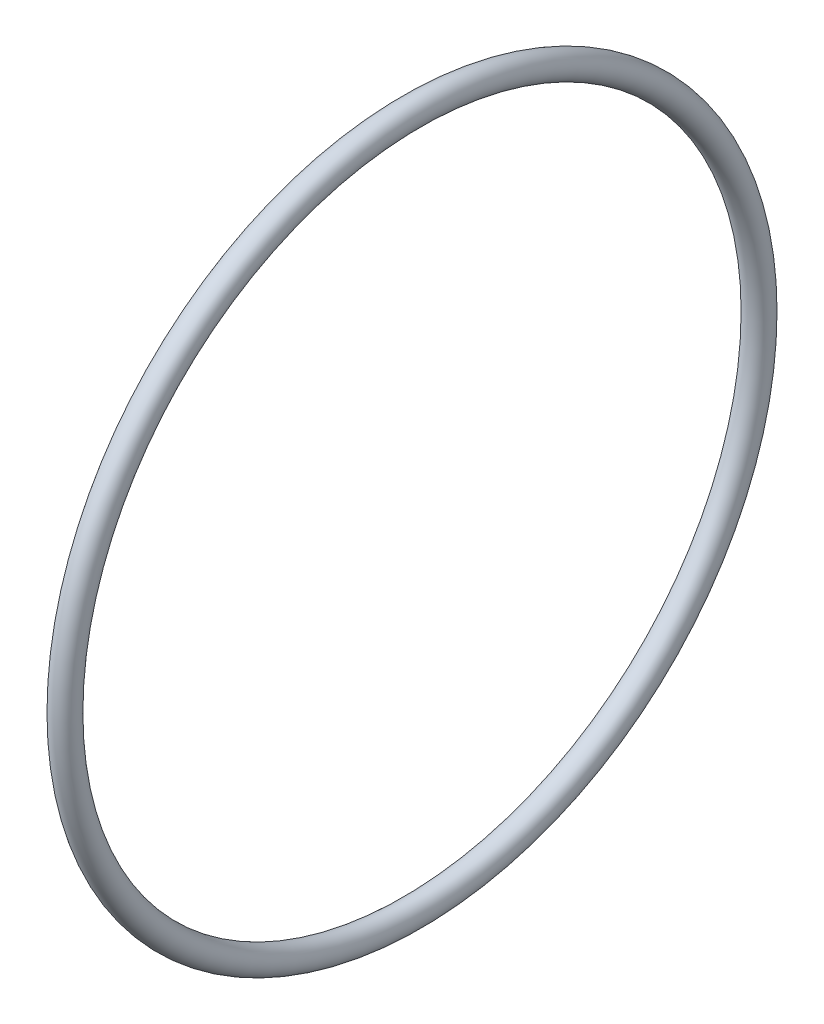
SolidWorks part; units mm, degrees
ref_plane "Front Plane" through (0, 0, 0) normal (0, 0, 1) x (1, 0, 0)
ref_plane "Top Plane" through (0, 0, 0) normal (0, 1, 0) x (1, 0, 0)
ref_plane "Right Plane" through (0, 0, 0) normal (1, 0, 0) x (0, 0, -1)
sketch "Sketch2" plane through (0, 0, 0) normal (0, 0, 1) x (1, 0, 0)
  line L0 (0, 0) -> (58.591, 0) construction
  line L2 (0, 0) -> (18.4, 0)
  line L3 (0, 0) -> (0, 2.5)
  line L4 (0, 2.5) -> (18.4, 2.5)
  line L5 (18.4, 0) -> (18.4, 2.5)
  line L6 (6, 2.5) -> (6, 6)
  line L11 (6, 6) -> (9.97, 6)
  line L16 (12.97, 6) -> (12.97, 3)
  line L17 (12.97, 3) -> (13.6304, 3)
  line L18 (13.6304, 3) -> (13.6304, 2.5)
  line L19 (13.6304, 2.5) -> (6, 2.5)
  line L22 (13.6304, 2.5) -> (16.1104, 2.5)
  line L23 (13.6304, 2.5) -> (13.6304, 4)
  line L24 (13.6304, 4) -> (16.1104, 4)
  line L25 (16.1104, 2.5) -> (16.1104, 4)
  line L27 (6, 6) -> (9.97, 6)
  line L28 (6, 6) -> (6, 9)
  line L29 (6, 9) -> (9.97, 9)
  line L30 (9.97, 6) -> (9.97, 9)
  line L31 (6, 9) -> (6, 8.25)
  line L32 (6, 8.25) -> (5, 8.25)
  line L33 (8.58, 22.001) -> (8.58, 12.476) construction
  line L34 (5, 12.476) -> (12.16, 12.476)
  line L35 (9.97, 9) -> (12.16, 9)
  line L36 (5, 7.5) -> (3, 7.5)
  line L37 (5, 8.25) -> (5, 12.476)
  line L38 (5, 7.5) -> (5, 14)
  line L39 (5, 14) -> (3, 14)
  line L40 (3, 7.5) -> (3, 14)
  line L41 (5, 22.001) -> (12.16, 22.001)
  line L42 (5, 22.001) -> (5, 30.1625)
  line L43 (5, 30.1625) -> (12.16, 30.1625)
  line L44 (12.16, 22.001) -> (12.16, 30.1625)
  line L49 (16.6304, 22.001) -> (16.6304, 7.5)
  line L51 (23.0104, 7.5) -> (23.0104, 6.5)
  line L54 (16.1104, 4) -> (13.6304, 4)
  line L56 (18.0304, 7.5) -> (23.0104, 7.5)
  line L57 (13.16, 22.001) -> (16.6304, 22.001)
  line L58 (16.1104, 3.5) -> (20.0104, 3.5)
  line L59 (29.9004, 14) -> (26.9004, 11)
  line L60 (4, 31.75) -> (18.0304, 31.75)
  line L61 (18.0304, 7.5) -> (23.0104, 7.5)
  line L62 (18.0304, 7.5) -> (18.0304, 12)
  line L63 (18.0304, 12) -> (23.0104, 12)
  line L64 (23.0104, 7.5) -> (23.0104, 12)
  line L65 (18.0304, 31.75) -> (18.0304, 12)
  line L66 (23.0104, 11) -> (26.9004, 11)
  line L67 (34.8004, 23) -> (31.3004, 19.5)
  line L68 (35.8004, 31) -> (38.7904, 33.99)
  line L69 (29.9004, 14) -> (29.9004, 15)
  line L70 (29.9004, 15) -> (22.9304, 15)
  line L71 (22.9304, 15) -> (21.0304, 15)
  line L72 (18.0304, 7.5) -> (16.6304, 7.5)
  line L73 (21.0304, 15) -> (21.0304, 43)
  line L74 (20.0304, 40) -> (10.0704, 40)
  line L75 (10.0704, 40) -> (4, 40)
  line L76 (21.0304, 43) -> (20.0304, 43)
  line L77 (22.9304, 15) -> (29.9004, 15)
  line L78 (22.9304, 15) -> (22.9304, 21)
  line L79 (22.9304, 21) -> (29.9004, 21)
  line L80 (29.9004, 15) -> (29.9004, 21)
  line L81 (10.0704, 40) -> (20.0304, 40)
  line L82 (10.0704, 40) -> (10.0704, 50)
  line L83 (10.0704, 50) -> (20.0304, 50)
  line L84 (20.0304, 40) -> (20.0304, 50)
  line L85 (4, 40) -> (4, 31.75)
  line L86 (12.97, 3) -> (12.97, 2.5)
  line L87 (31.3004, 19.5) -> (29.9004, 19.5)
  line L88 (21.51, 63.5) -> (21.51, 44)
  line L89 (21.51, 63.5) -> (25.9304, 63.5)
  line L90 (25.9304, 63.5) -> (25.9304, 25)
  line L91 (27.8304, 25) -> (25.9304, 25)
  line L92 (10.0704, 48) -> (9, 48)
  line L93 (9, 48) -> (9, 53.476)
  line L94 (9, 53.476) -> (20.0304, 53.476)
  line L95 (20.0304, 53.476) -> (20.0304, 50)
  line L96 (14.5152, 63.001) -> (14.5152, 53.476) construction
  line L97 (9, 63.001) -> (20.0304, 63.001)
  line L98 (9, 63.001) -> (9, 68.2625)
  line L99 (9, 68.2625) -> (20.0304, 68.2625)
  line L100 (20.0304, 63.001) -> (20.0304, 68.2625)
  line L101 (12.97, 6) -> (11.97, 6)
  line L102 (9, 42.5) -> (5, 42.5)
  line L103 (9, 42.5) -> (9, 55)
  line L104 (9, 55) -> (5, 55)
  line L105 (5, 42.5) -> (5, 55)
  line L106 (9.97, 6) -> (10.87, 6)
  line L107 (27.8304, 25) -> (34.8004, 25)
  line L108 (34.8004, 25) -> (34.8004, 23)
  line L109 (0, 0) -> (-2, 0)
  line L110 (0, 0) -> (0, 11)
  line L111 (27.8304, 25) -> (34.8004, 25)
  line L112 (27.8304, 25) -> (27.8304, 32.5)
  line L113 (27.8304, 32.5) -> (34.8004, 32.5)
  line L114 (34.8004, 25) -> (34.8004, 32.5)
  line L115 (35.8004, 31) -> (34.8004, 31)
  line L116 (27.8304, 32.5) -> (27.8304, 64.5)
  line L117 (21.1827, 74.025) -> (6.8477, 74.025)
  line L118 (6.8477, 74.025) -> (6.8477, 76.2)
  line L119 (38.7904, 47.29) -> (30.8304, 55.25)
  line L120 (0, 11) -> (-2, 11)
  line L121 (38.7904, 43.815) -> (30.8529, 43.815)
  line L123 (-4.8, 69.85) -> (1.55, 76.2)
  line L124 (38.7904, 47.29) -> (38.7904, 33.99)
  line L125 (-2, 0) -> (-2, 11)
  line L126 (38.7904, 37.465) -> (30.8529, 37.465)
  line L127 (30.8529, 43.815) -> (30.8529, 37.465)
  line L128 (6, 2.5) -> (6, 0)
  line L129 (0, 63.5) -> (0, 30)
  line L132 (5, 63.5) -> (0, 63.5)
  line L136 (-1.8, 30) -> (-11.76, 30)
  line L138 (-13.76, 25.4) -> (-2, 25.4)
  line L139 (-2, 25.4) -> (-2, 11.5)
  line L140 (27.8304, 64.5) -> (21.1827, 64.5)
  line L141 (-1.8, 30) -> (-11.76, 30)
  line L142 (-1.8, 30) -> (-1.8, 39)
  line L143 (-1.8, 39) -> (-11.76, 39)
  line L144 (-11.76, 30) -> (-11.76, 39)
  line L145 (21.1827, 64.5) -> (21.1827, 74.025)
  line L146 (-12.76, 37) -> (-12.76, 47.29)
  line L147 (-12.76, 37) -> (-11.76, 37)
  line L148 (30.8304, 55.25) -> (30.8304, 76.2)
  line L149 (11.97, 6) -> (11.97, 5.45)
  line L154 (-2, 11.5) -> (1, 11.5)
  line L155 (5, 60.6197) -> (24.05, 60.6197)
  line L160 (5, 60.6197) -> (5, 55.8572)
  line L161 (5, 55.8572) -> (24.05, 55.8572)
  line L166 (24.05, 60.6197) -> (24.05, 55.8572)
  line L167 (5, 60.6197) -> (24.05, 55.8572) construction
  line L172 (5, 55.8572) -> (24.05, 60.6197) construction
  line L173 (24.05, 62.2072) -> (25.9304, 62.2072)
  line L174 (11.97, 5.45) -> (10.87, 5.45)
  line L175 (10.87, 6) -> (10.87, 5.45)
  line L176 (24.05, 62.2072) -> (24.05, 54.2697)
  line L177 (24.05, 54.2697) -> (25.9304, 54.2697)
  line L178 (25.9304, 62.2072) -> (25.9304, 54.2697)
  line L179 (24.05, 62.2072) -> (25.9304, 54.2697) construction
  line L180 (24.05, 54.2697) -> (25.9304, 62.2072) construction
  line L181 (3, 19.6197) -> (15.7, 19.6197)
  line L182 (3, 19.6197) -> (3, 14.8572)
  line L183 (3, 14.8572) -> (15.7, 14.8572)
  line L184 (15.7, 19.6197) -> (15.7, 14.8572)
  line L185 (3, 19.6197) -> (15.7, 14.8572) construction
  line L186 (3, 14.8572) -> (15.7, 19.6197) construction
  line L187 (15.7, 21.2072) -> (16.6304, 21.2072)
  line L188 (15.7, 21.2072) -> (15.7, 13.2697)
  line L189 (15.7, 13.2697) -> (16.6304, 13.2697)
  line L190 (16.6304, 21.2072) -> (16.6304, 13.2697)
  line L191 (15.7, 21.2072) -> (16.6304, 13.2697) construction
  line L192 (15.7, 13.2697) -> (16.6304, 21.2072) construction
  line L193 (1, 11.5) -> (1, 6.5)
  line L194 (1, 6.5) -> (3, 6.5)
  line L195 (23.0104, 6.5) -> (20.0104, 3.5)
  line L196 (5, 63.5) -> (5, 42.5)
  line L197 (5, 42.5) -> (3, 42.5)
  line L198 (3, 42.5) -> (3, 6.5)
  line L199 (6, 0) -> (12.97, 0)
  line L200 (12.97, 0) -> (12.97, 2.5)
  line L201 (18.0304, 31.75) -> (18.0304, 35.875)
  line L202 (18.0304, 35.875) -> (21.0304, 35.875)
  line L203 (30.8304, 76.2) -> (6.8477, 76.2)
  line L204 (3.4027, 69.85) -> (7.8477, 69.85) construction
  line L205 (7.8477, 67.4687) -> (26.8977, 67.4688)
  line L206 (7.8477, 74.025) -> (7.8477, 64.5)
  line L207 (7.8477, 64.5) -> (-1.8, 64.5)
  line L208 (-1.8, 64.5) -> (-1.8, 39)
  line L209 (-12.76, 47.29) -> (-4.8, 55.25)
  line L210 (-4.8, 55.25) -> (-4.8, 69.85)
  line L211 (7.8477, 67.4687) -> (7.8477, 72.2313)
  line L212 (7.8477, 72.2313) -> (26.8977, 72.2313)
  line L213 (26.8977, 67.4688) -> (26.8977, 72.2313)
  line L214 (26.8977, 73.8187) -> (30.8304, 73.8187)
  line L215 (26.8977, 73.8187) -> (26.8977, 65.8813)
  line L216 (26.8977, 65.8813) -> (30.8304, 65.8813)
  line L217 (30.8304, 73.8187) -> (30.8304, 65.8813)
  line L218 (3.4027, 72.2313) -> (25.6277, 72.2313)
  line L219 (3.4027, 72.2313) -> (3.4027, 67.4687)
  line L220 (3.4027, 67.4687) -> (25.6277, 67.4687)
  line L221 (25.6277, 72.2313) -> (25.6277, 67.4687)
  line L222 (25.6277, 69.85) -> (21.1827, 69.85) construction
  line L223 (21.51, 44) -> (22.9304, 44)
  line L224 (22.9304, 44) -> (22.9304, 21)
  line L225 (13.6304, 4) -> (13.6304, 12.2697)
  line L226 (13.6304, 12.2697) -> (13.16, 12.2697)
  line L227 (13.16, 12.2697) -> (13.16, 22.001)
  line L228 (12.16, 9) -> (12.16, 12.476)
  line L229 (-1.8, 30) -> (0, 30)
  line L230 (9, 65.6317) -> (3.4027, 65.6317) construction
  line L231 (20.0304, 65.6317) -> (25.6277, 65.6317) construction
  line L232 (1.55, 76.2) -> (6.8477, 76.2)
  line L233 (-11.76, 30) -> (-13.76, 30)
  line L234 (-13.76, 30) -> (-13.76, 25.4)
  circle A0 centre (26.8804, 25.95) radius 0.95
  circle A1 centre (21.9804, 15.95) radius 0.95
  circle A2 centre (17.3304, 8.2) radius 0.7
  circle A3 centre (10.42, 6.45) radius 0.45
  circle A4 centre (-0.9, 30.9) radius 0.9
  point P7 (24.9902, 58.2385)
  point P131 (16.1652, 17.2385)
  point P135 (14.525, 58.2385)
  point P146 (9.35, 17.2385)
sketch "Sketch3" plane through (0, 0, 0) normal (0, 0, 1) x (1, 0, 0)
  circle A0 centre (26.8804, 25.95) radius 0.95 construction
  circle A1 centre (26.8804, 25.95) radius 0.95
revolve "Revolve1" add sketch "Sketch3" angle 360 about L0
